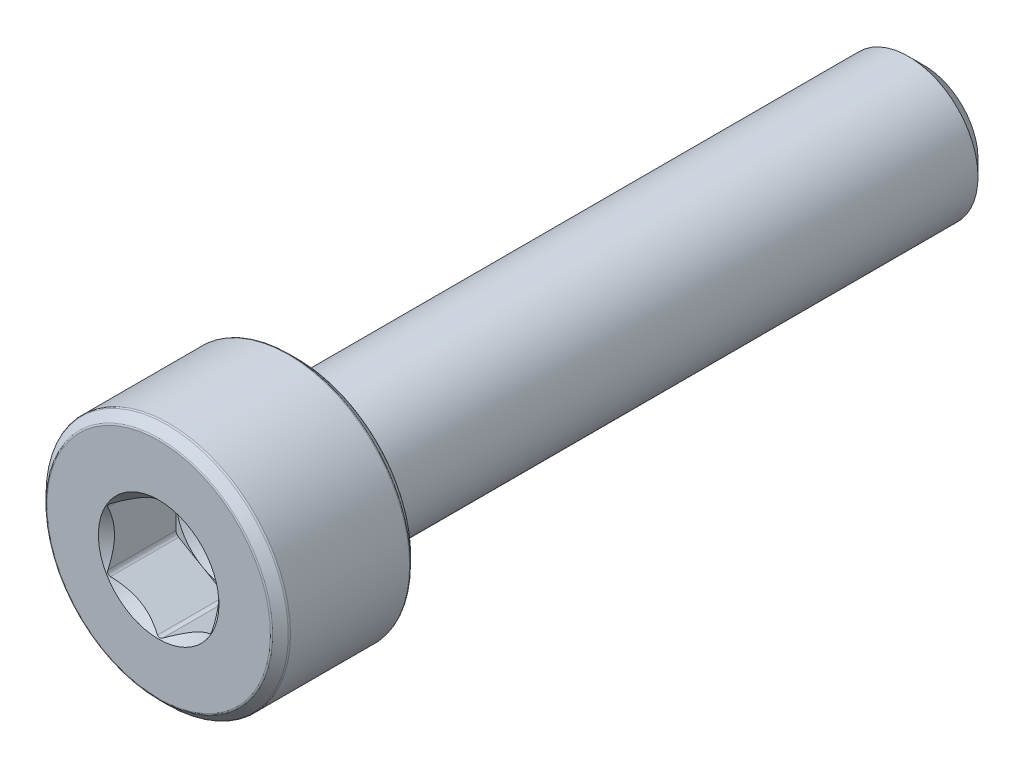
SolidWorks part; units mm, degrees
ref_plane "Front Plane" through (0, 0, 0) normal (0, 0, 1) x (1, 0, 0)
ref_plane "Top Plane" through (0, 0, 0) normal (0, 1, 0) x (1, 0, 0)
ref_plane "Right Plane" through (0, 0, 0) normal (1, 0, 0) x (0, 0, -1)
sketch "Sketch1" plane through (0, 0, 0) normal (1, 0, 0) x (0, 0, -1)
  line L0 (-11, 0) -> (11, 0) construction
  line L1 (-11, 0) -> (-11, 3.5)
  line L2 (-11, 3.5) -> (-7, 3.5)
  line L3 (-7, 3.5) -> (-7, 2)
  line L4 (-7, 2) -> (10.5453, 2)
  line L5 (10.9562, 2.0758) -> (11.3062, 1.4696) construction
  line L6 (11.3062, 1.4696) -> (11.6562, 2.0758) construction
  line L7 (11.6562, 2.0758) -> (10.9562, 2.0758) construction
  line L8 (10.5453, 2) -> (11, 1.5453)
  line L9 (11, 1.5453) -> (11, 0)
  line L10 (11, 2) -> (11.6125, 2) construction
  line L11 (11.3062, 2.0758) -> (11.3062, 2) construction
  line L12 (11.3062, 2) -> (11.3062, 1.5453) construction
  line L13 (11.3062, 1.5453) -> (11.3062, 1.4696) construction
  line L14 (11.2625, 1.5453) -> (11.35, 1.5453)
  line L15 (10.9781, 2.0379) -> (11.6344, 2.0379)
  line L16 (11.35, 1.5453) -> (11.6344, 2.0379)
  line L17 (11.2625, 1.5453) -> (10.9781, 2.0379)
  line L18 (-11, 1.5) -> (-9, 1.5)
  line L19 (-9, 1.5) -> (-9, 0)
  line L20 (8.55, 2) -> (8.55, -2) construction
  point P20 (11.3062, 2.0379)
  point P22 (8.55, -2)
  point P28 (8.55, 0)
  point P29 (10.5453, -2)
  dimension "Head Diameter" = 7
  dimension "Length" = 18
  dimension "Head Height" = 4
  dimension "Thread Size" = 4
  dimension "D1" = 45
  dimension "Thread Pitch" = 0.7
  dimension "D3" = 0.0875
  dimension "Drive Size" = 3
  dimension "D4" = 2.45
  dimension "D5" = 2
sketch "Sketch3" plane through (0, 0, 0) normal (1, 0, 0) x (0, 0, -1)
  line L0 (-11, 3.2103) -> (-11, 1.5)
  line L1 (-11, 1.5) -> (-9, 1.5)
  line L2 (-9, 1.5) -> (-9, 0)
  line L3 (-9, 0) -> (11, 0)
  line L4 (11, 0) -> (11, 1.5453)
  line L5 (11, 1.5453) -> (10.5453, 2)
  line L6 (10.5453, 2) -> (-7, 2)
  line L7 (-7, 2) -> (-7, 3.2103)
  line L8 (-7.2897, 3.5) -> (-10.7103, 3.5)
  line L9 (-10.9808, 3.2567) -> (-10.7567, 3.4808)
  line L11 (-11, 3.5) -> (-7, 3.5) construction
  line L12 (-7.2433, 3.4808) -> (-7.0192, 3.2567)
  arc A5 (-7.0192, 3.2567) -> (-7, 3.2103) centre (-7.0656, 3.2103) cw
  arc A6 (-7.2897, 3.5) -> (-7.2433, 3.4808) centre (-7.2897, 3.4344) cw
  arc A7 (-10.7103, 3.5) -> (-10.7567, 3.4808) centre (-10.7103, 3.4344) ccw
  arc A8 (-11, 3.2103) -> (-10.9808, 3.2567) centre (-10.9344, 3.2103) cw
  point P17 (-9, 3.5)
  point P29 (-11, 3.2375)
  dimension "D3" = 0.0656
  dimension "D1" = 45
  dimension "D2" = 0.2625
revolve "Revolve1" add sketch "Sketch3" angle 360 about L0
sketch "Sketch4" plane through (0, 0, 11) normal (0, 0, 1) x (1, 0, 0)
  line L1 (0, 1.7321) -> (-1.5, 0.866)
  line L2 (-1.5, 0.866) -> (-1.5, -0.866)
  line L3 (-1.5, -0.866) -> (0, -1.7321)
  line L4 (0, -1.7321) -> (1.5, -0.866)
  line L5 (1.5, -0.866) -> (1.5, 0.866)
  line L6 (1.5, 0.866) -> (0, 1.7321)
  circle A0 centre (0, 0) radius 1.5 construction
extrude "Cut-Extrude1" cut sketch "Sketch4" against normal up to vertex (2 mm away) up to point (0, 1.5, 9)
sketch "Sketch5" plane through (0, 0, 11) normal (0, 0, 1) x (1, 0, 0)
  circle A0 centre (0, 0) radius 1.7321
extrude "Cut-Extrude2" cut sketch "Sketch5" against normal up to next (2 mm away) draft 45
sketch "Sketch10" plane through (0, 0, 9) normal (0, 0, 1) x (1, 0, 0)
  line L0 (1.5, 0.866) -> (1.5, -0.866) construction
  circle A0 centre (0, 0) radius 1.5
extrude "Cut-Extrude3" cut sketch "Sketch10" against normal through all draft 60
fillet "Fillet1" radius 0.15 6 edges at (-1.5, 0.866, 10) (0, 1.7321, 10) (1.5, 0.866, 10) (1.5, -0.866, 10) (0, -1.7321, 10) (-1.5, -0.866, 10)
sketch "Sketch6" plane through (0, 0, -11) normal (0, 0, -1) x (-1, 0, 0)
  circle A0 centre (0, 0) radius 2 construction
  circle A1 centre (0, 0) radius 2
curve "Helix/Spiral1" [suppressed] pitch 0.7 height 18.7 turns 26.7143
sketch "Sketch7" plane through (0, 0, 0) normal (1, 0, 0) x (0, 0, -1)
  line L0 (11.2625, 1.5453) -> (11.35, 1.5453) construction
  line L1 (11.2625, 1.5453) -> (10.9781, 2.0379) construction
  line L2 (10.9781, 2.0379) -> (11.6344, 2.0379) construction
  line L3 (11.35, 1.5453) -> (11.6344, 2.0379) construction
  line L4 (11.2625, 1.5453) -> (11.35, 1.5453)
  line L5 (11.2625, 1.5453) -> (10.9781, 2.0379)
  line L6 (10.9781, 2.0379) -> (11.6344, 2.0379)
  line L7 (11.35, 1.5453) -> (11.6344, 2.0379)
sweep "Cut-Sweep1" [suppressed] cut profiles "Sketch7" path "Helix/Spiral1"
sketch "Sketch11" plane through (0, 0, 0) normal (1, 0, 0) x (0, 0, -1)
  line L0 (-7, 2.175) -> (-6.825, 2) construction
  line L1 (-7, 3.5) -> (-7, 2) construction
  line L2 (-7, 2) -> (10.5453, 2) construction
  line L3 (-6.825, 2) -> (-6.65, 2)
  line L4 (-6.65, 2) -> (-4.65, 0)
  line L5 (-11, 0) -> (11, 0) construction
  line L6 (-4.65, 0) -> (-7, 0)
  line L7 (-7, 0) -> (-7, 2.175) construction
  line L8 (-7, 2.175) -> (-8.134, 2.175)
  line L9 (-8.134, 2.175) -> (-8.134, 0)
  line L10 (-8.134, 0) -> (-7, 0)
  arc A0 (-6.825, 2) -> (-7, 2.175) centre (-6.825, 2.175) cw
  dimension "D1" = 45
  dimension "D2" = 0.175
  dimension "D3" = 45
  dimension "D4" = 0.35
revolve "Revolve2" [suppressed] add sketch "Sketch11" angle 360 about L6
equation "\"D3@Sketch1\" = \"Thread Pitch@Sketch1\" / 8"
equation "\"D4@Sketch1\" = \"Thread Pitch@Sketch1\" * 3.5"
equation "\"D3@Helix/Spiral1\" = \"Length@Sketch1\" + \"Thread Pitch@Sketch1\""
equation "\"D4@Helix/Spiral1\" = \"Thread Pitch@Sketch1\""
equation "\"D5@Sketch1\"=\"Head Height@Sketch1\"*0.5"
equation "\"D2@Sketch3\"=\"Head Diameter@Sketch1\" *0.0375"
equation "\"D2@Sketch11\"=\"Thread Pitch@Sketch1\" / 4"
equation "\"D4@Sketch11\"=\"Thread Pitch@Sketch1\"/2"
equation "\"D1@Fillet1\"=\"Drive Size@Sketch1\"*0.05"
equation "\"D1@Fillet1\" = \"Drive Size@Sketch1\" * 0.05"
equation "\"D3@Sketch3\"=\"D2@Sketch3\"*0.25"
